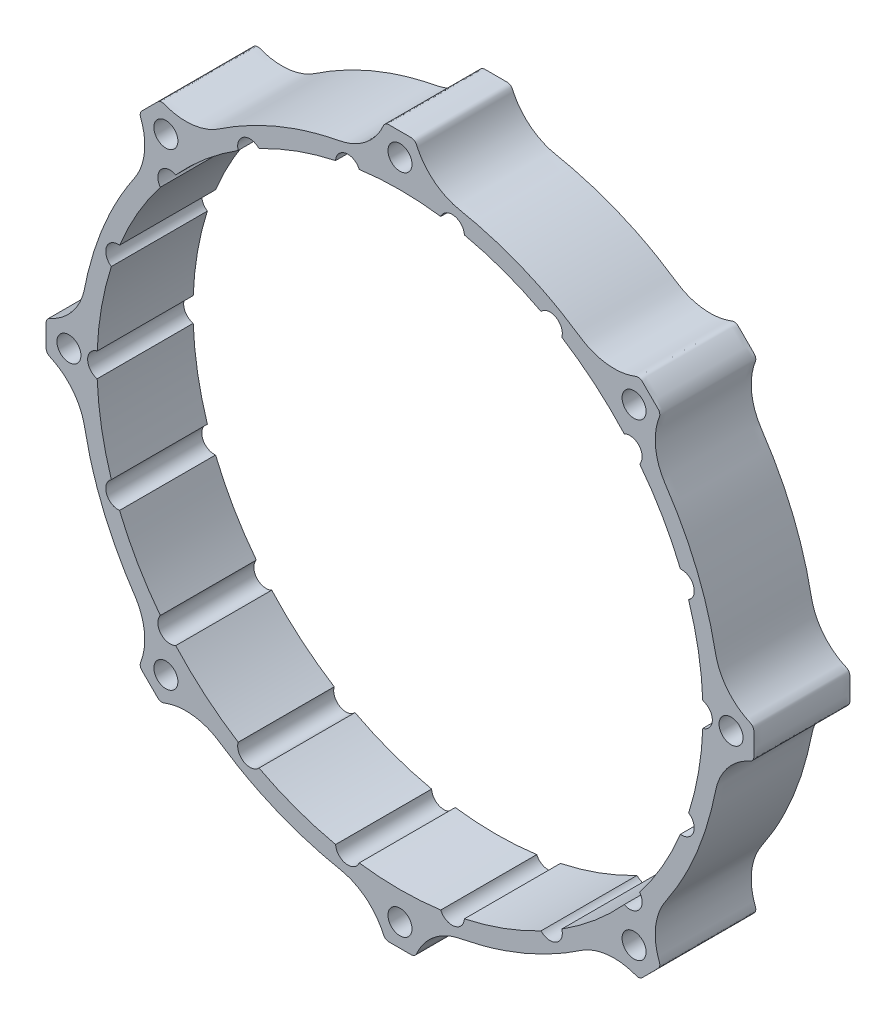
SolidWorks part; units mm, degrees
material "7075-T6, Plate (SS)"
ref_plane "Front Plane" through (0, 0, 0) normal (0, 0, 1) x (1, 0, 0)
ref_plane "Top Plane" through (0, 0, 0) normal (0, 1, 0) x (1, 0, 0)
ref_plane "Right Plane" through (0, 0, 0) normal (1, 0, 0) x (0, 0, -1)
sketch "Sketch1" plane through (0, 0, 0) normal (0, 0, 1) x (1, 0, 0)
  line L0 (0, 0) -> (0, 55.17) construction
  line L1 (0, 0) -> (-8.6824, 49.2404) construction
  arc A0 (-6.7951, 50.0407) -> (-10.7296, 49.347) centre (-8.6824, 49.2404) ccw
  arc A36 (-10.7296, 49.347) -> (-23.5003, 44.6989) centre (0, 0) ccw
  circle A53 centre (0, 0) radius 50 construction
  arc A54 (10.7296, 49.347) -> (6.7951, 50.0407) centre (8.6824, 49.2404) ccw
  arc A55 (26.9602, 42.7012) -> (23.5003, 44.6989) centre (25, 43.3013) ccw
  arc A56 (39.939, 30.9051) -> (37.3709, 33.9656) centre (38.3022, 32.1394) ccw
  arc A57 (48.1006, 15.3814) -> (46.7341, 19.1356) centre (46.9846, 17.101) ccw
  arc A58 (50.4605, -1.9976) -> (50.4605, 1.9976) centre (50, 0) ccw
  arc A59 (46.7341, -19.1356) -> (48.1006, -15.3814) centre (46.9846, -17.101) ccw
  arc A60 (37.3709, -33.9656) -> (39.939, -30.9051) centre (38.3022, -32.1394) ccw
  arc A61 (23.5003, -44.6989) -> (26.9602, -42.7012) centre (25, -43.3013) ccw
  arc A62 (6.7951, -50.0407) -> (10.7296, -49.347) centre (8.6824, -49.2404) ccw
  arc A63 (-10.7296, -49.347) -> (-6.7951, -50.0407) centre (-8.6824, -49.2404) ccw
  arc A64 (-26.9602, -42.7012) -> (-23.5003, -44.6989) centre (-25, -43.3013) ccw
  arc A65 (-39.939, -30.9051) -> (-37.3709, -33.9656) centre (-38.3022, -32.1394) ccw
  arc A66 (-48.1006, -15.3814) -> (-46.7341, -19.1356) centre (-46.9846, -17.101) ccw
  arc A67 (-50.4605, 1.9976) -> (-50.4605, -1.9976) centre (-50, 0) ccw
  arc A68 (-46.7341, 19.1356) -> (-48.1006, 15.3814) centre (-46.9846, 17.101) ccw
  arc A69 (-37.3709, 33.9656) -> (-39.939, 30.9051) centre (-38.3022, 32.1394) ccw
  arc A70 (-23.5003, 44.6989) -> (-26.9602, 42.7012) centre (-25, 43.3013) ccw
  arc A71 (6.7951, 50.0407) -> (-6.7951, 50.0407) centre (0, 0) ccw
  arc A72 (23.5003, 44.6989) -> (10.7296, 49.347) centre (0, 0) ccw
  arc A73 (46.7341, 19.1356) -> (39.939, 30.9051) centre (0, 0) ccw
  arc A74 (37.3709, 33.9656) -> (26.9602, 42.7012) centre (0, 0) ccw
  arc A75 (50.4605, 1.9976) -> (48.1006, 15.3814) centre (0, 0) ccw
  arc A76 (48.1006, -15.3814) -> (50.4605, -1.9976) centre (0, 0) ccw
  arc A77 (39.939, -30.9051) -> (46.7341, -19.1356) centre (0, 0) ccw
  arc A78 (26.9602, -42.7012) -> (37.3709, -33.9656) centre (0, 0) ccw
  arc A79 (10.7296, -49.347) -> (23.5003, -44.6989) centre (0, 0) ccw
  arc A80 (-6.7951, -50.0407) -> (6.7951, -50.0407) centre (0, 0) ccw
  arc A81 (-23.5003, -44.6989) -> (-10.7296, -49.347) centre (0, 0) ccw
  arc A82 (-37.3709, -33.9656) -> (-26.9602, -42.7012) centre (0, 0) ccw
  arc A83 (-46.7341, -19.1356) -> (-39.939, -30.9051) centre (0, 0) ccw
  arc A84 (-50.4605, -1.9976) -> (-48.1006, -15.3814) centre (0, 0) ccw
  arc A85 (-48.1006, 15.3814) -> (-50.4605, 1.9976) centre (0, 0) ccw
  arc A86 (-39.939, 30.9051) -> (-46.7341, 19.1356) centre (0, 0) ccw
  arc A87 (-26.9602, 42.7012) -> (-37.3709, 33.9656) centre (0, 0) ccw
  spline S1 degree 3 poles (2.8886, 58.0903) (2.8604, 58.1497) (2.8053, 58.2691) (2.7273, 58.4532) (2.6522, 58.562) (2.6097, 58.6121) (2.4833, 58.7614) (2.3195, 58.8684) (2.132, 58.9243) (2.1013, 58.9334) (2.039, 58.9487) (1.9428, 58.9658) (1.8787, 58.9658) (1.8466, 58.9658) (1.8146, 58.9658) (1.7505, 58.9658) (1.6544, 58.9658) (1.5903, 58.9658) (1.5583, 58.9658) (0.5194, 58.9658) (-0.5194, 58.9658) (-1.5583, 58.9658) (-1.5903, 58.9658) (-1.6544, 58.9658) (-1.7505, 58.9658) (-1.8146, 58.9658) (-1.8466, 58.9658) (-1.8787, 58.9658) (-1.9428, 58.9658) (-2.039, 58.9487) (-2.1013, 58.9334) (-2.132, 58.9243) (-2.3195, 58.8684) (-2.4833, 58.7614) (-2.6097, 58.6121) (-2.6522, 58.562) (-2.7273, 58.4532) (-2.8053, 58.2691) (-2.8604, 58.1497) (-2.8886, 58.0903) (-3.9043, 55.9453) (-5.5918, 54.2764) (-7.7481, 53.2847) (-8.2352, 53.0607) (-9.2456, 52.691) (-10.8423, 52.3981) (-11.8892, 52.165) (-12.4107, 52.0406) (-17.936, 50.7229) (-23.1839, 48.5492) (-28.0226, 45.574) (-28.4793, 45.2931) (-29.3844, 44.7177) (-30.7205, 43.7957) (-31.6964, 43.3428) (-32.1993, 43.1567) (-34.5203, 42.2981) (-36.9949, 42.3196) (-39.3007, 43.2183) (-39.3011, 43.2185) (-39.3019, 43.2188) (-39.3031, 43.2193) (-39.3039, 43.2196) (-39.3043, 43.2198) (-39.3047, 43.2199) (-39.3055, 43.2202) (-39.3067, 43.2207) (-39.3075, 43.221) (-39.3079, 43.2212) (-39.3103, 43.2221) (-39.3127, 43.223) (-39.3151, 43.224) (-39.3155, 43.2241) (-39.3163, 43.2245) (-39.3175, 43.2249) (-39.3183, 43.2252) (-39.3187, 43.2254) (-39.3191, 43.2255) (-39.3199, 43.2259) (-39.3211, 43.2263) (-39.3219, 43.2266) (-39.3224, 43.2268) (-39.5998, 43.3338) (-39.8966, 43.3148) (-40.1582, 43.1733) (-40.1864, 43.158) (-40.2413, 43.1248) (-40.3214, 43.0689) (-40.3667, 43.0236) (-40.3894, 43.0009) (-40.412, 42.9783) (-40.4573, 42.933) (-40.5253, 42.865) (-40.5706, 42.8197) (-40.5933, 42.797) (-41.3279, 42.0624) (-42.0624, 41.3279) (-42.797, 40.5933) (-42.8197, 40.5706) (-42.865, 40.5253) (-42.933, 40.4573) (-42.9783, 40.412) (-43.0009, 40.3894) (-43.0236, 40.3667) (-43.0689, 40.3214) (-43.1248, 40.2413) (-43.158, 40.1864) (-43.1733, 40.1582) (-43.3148, 39.8966) (-43.3338, 39.5998) (-43.2268, 39.3224) (-43.2266, 39.3219) (-43.2263, 39.3211) (-43.2259, 39.3199) (-43.2255, 39.3191) (-43.2254, 39.3187) (-43.2252, 39.3183) (-43.2249, 39.3175) (-43.2245, 39.3163) (-43.2241, 39.3155) (-43.224, 39.3151) (-43.223, 39.3127) (-43.2221, 39.3103) (-43.2212, 39.3079) (-43.221, 39.3075) (-43.2207, 39.3067) (-43.2202, 39.3055) (-43.2199, 39.3047) (-43.2198, 39.3043) (-43.2196, 39.3039) (-43.2193, 39.3031) (-43.2188, 39.3019) (-43.2185, 39.3011) (-43.2183, 39.3007) (-42.3196, 36.9949) (-42.2981, 34.5203) (-43.1567, 32.1993) (-43.3428, 31.6964) (-43.7957, 30.7205) (-44.7177, 29.3844) (-45.2931, 28.4793) (-45.574, 28.0226) (-48.5492, 23.1839) (-50.7229, 17.936) (-52.0406, 12.4107) (-52.165, 11.8892) (-52.3981, 10.8423) (-52.691, 9.2456) (-53.0607, 8.2352) (-53.2847, 7.7481) (-54.3188, 5.4997) (-56.0838, 3.7651) (-58.3498, 2.7702) (-58.3502, 2.77) (-58.3509, 2.7697) (-58.3521, 2.7692) (-58.3529, 2.7688) (-58.3533, 2.7687) (-58.3537, 2.7685) (-58.3545, 2.7681) (-58.3557, 2.7676) (-58.3565, 2.7673) (-58.3569, 2.7671) (-58.3592, 2.7661) (-58.3616, 2.765) (-58.364, 2.764) (-58.3644, 2.7638) (-58.3651, 2.7635) (-58.3663, 2.7629) (-58.3671, 2.7626) (-58.3675, 2.7624) (-58.3679, 2.7623) (-58.3687, 2.7619) (-58.3699, 2.7614) (-58.3707, 2.761) (-58.3711, 2.7609) (-58.643, 2.6403) (-58.8394, 2.417) (-58.9243, 2.132) (-58.9334, 2.1013) (-58.9487, 2.039) (-58.9658, 1.9428) (-58.9658, 1.8787) (-58.9658, 1.8466) (-58.9658, 1.8146) (-58.9658, 1.7505) (-58.9658, 1.6544) (-58.9658, 1.5903) (-58.9658, 1.5583) (-58.9658, 0.5194) (-58.9658, -0.5194) (-58.9658, -1.5583) (-58.9658, -1.5903) (-58.9658, -1.6544) (-58.9658, -1.7505) (-58.9658, -1.8146) (-58.9658, -1.8466) (-58.9658, -1.8787) (-58.9658, -1.9428) (-58.9487, -2.039) (-58.9334, -2.1013) (-58.9243, -2.132) (-58.8394, -2.417) (-58.643, -2.6403) (-58.3711, -2.7609) (-58.3707, -2.761) (-58.3699, -2.7614) (-58.3687, -2.7619) (-58.3679, -2.7623) (-58.3675, -2.7624) (-58.3671, -2.7626) (-58.3663, -2.7629) (-58.3651, -2.7635) (-58.3644, -2.7638) (-58.364, -2.764) (-58.3616, -2.765) (-58.3592, -2.7661) (-58.3569, -2.7671) (-58.3565, -2.7673) (-58.3557, -2.7676) (-58.3545, -2.7681) (-58.3537, -2.7685) (-58.3533, -2.7687) (-58.3529, -2.7688) (-58.3521, -2.7692) (-58.3509, -2.7697) (-58.3502, -2.77) (-58.3498, -2.7702) (-56.0838, -3.7651) (-54.3188, -5.4997) (-53.2847, -7.7481) (-53.0607, -8.2352) (-52.691, -9.2456) (-52.3981, -10.8423) (-52.165, -11.8892) (-52.0406, -12.4107) (-50.7229, -17.936) (-48.5492, -23.1839) (-45.574, -28.0226) (-45.2931, -28.4793) (-44.7177, -29.3844) (-43.7957, -30.7205) (-43.3428, -31.6964) (-43.1567, -32.1993) (-42.2981, -34.5203) (-42.3196, -36.9949) (-43.2183, -39.3007) (-43.2185, -39.3011) (-43.2188, -39.3019) (-43.2193, -39.3031) (-43.2196, -39.3039) (-43.2198, -39.3043) (-43.2199, -39.3047) (-43.2202, -39.3055) (-43.2207, -39.3067) (-43.221, -39.3075) (-43.2212, -39.3079) (-43.2221, -39.3103) (-43.223, -39.3127) (-43.224, -39.3151) (-43.2241, -39.3155) (-43.2245, -39.3163) (-43.2249, -39.3175) (-43.2252, -39.3183) (-43.2254, -39.3187) (-43.2255, -39.3191) (-43.2259, -39.3199) (-43.2263, -39.3211) (-43.2266, -39.3219) (-43.2268, -39.3224) (-43.3338, -39.5998) (-43.3148, -39.8966) (-43.1733, -40.1582) (-43.158, -40.1864) (-43.1248, -40.2413) (-43.0689, -40.3214) (-43.0236, -40.3667) (-43.0009, -40.3894) (-42.9783, -40.412) (-42.933, -40.4573) (-42.865, -40.5253) (-42.8197, -40.5706) (-42.797, -40.5933) (-42.0624, -41.3279) (-41.3279, -42.0624) (-40.5933, -42.797) (-40.5706, -42.8197) (-40.5253, -42.865) (-40.4573, -42.933) (-40.412, -42.9783) (-40.3894, -43.0009) (-40.3667, -43.0236) (-40.3214, -43.0689) (-40.2413, -43.1248) (-40.1864, -43.158) (-40.1582, -43.1733) (-39.8966, -43.3148) (-39.5998, -43.3338) (-39.3224, -43.2268) (-39.3219, -43.2266) (-39.3211, -43.2263) (-39.3199, -43.2259) (-39.3191, -43.2255) (-39.3187, -43.2254) (-39.3183, -43.2252) (-39.3175, -43.2249) (-39.3163, -43.2245) (-39.3155, -43.2241) (-39.3151, -43.224) (-39.3127, -43.223) (-39.3103, -43.2221) (-39.3079, -43.2212) (-39.3075, -43.221) (-39.3067, -43.2207) (-39.3055, -43.2202) (-39.3047, -43.2199) (-39.3043, -43.2198) (-39.3039, -43.2196) (-39.3031, -43.2193) (-39.3019, -43.2188) (-39.3011, -43.2185) (-39.3007, -43.2183) (-36.9949, -42.3196) (-34.5203, -42.2981) (-32.1993, -43.1567) (-31.6964, -43.3428) (-30.7205, -43.7957) (-29.3844, -44.7177) (-28.4793, -45.2931) (-28.0226, -45.574) (-23.1839, -48.5492) (-17.936, -50.7229) (-12.4107, -52.0406) (-11.8892, -52.165) (-10.8423, -52.3981) (-9.2456, -52.691) (-8.2352, -53.0607) (-7.7481, -53.2847) (-5.4997, -54.3188) (-3.7651, -56.0838) (-2.7702, -58.3498) (-2.77, -58.3502) (-2.7697, -58.3509) (-2.7692, -58.3521) (-2.7688, -58.3529) (-2.7687, -58.3533) (-2.7685, -58.3537) (-2.7681, -58.3545) (-2.7676, -58.3557) (-2.7673, -58.3565) (-2.7671, -58.3569) (-2.7661, -58.3592) (-2.765, -58.3616) (-2.764, -58.364) (-2.7638, -58.3644) (-2.7635, -58.3651) (-2.7629, -58.3663) (-2.7626, -58.3671) (-2.7624, -58.3675) (-2.7623, -58.3679) (-2.7619, -58.3687) (-2.7614, -58.3699) (-2.761, -58.3707) (-2.7609, -58.3711) (-2.6403, -58.643) (-2.417, -58.8394) (-2.132, -58.9243) (-2.1013, -58.9334) (-2.039, -58.9487) (-1.9428, -58.9658) (-1.8787, -58.9658) (-1.8466, -58.9658) (-1.8146, -58.9658) (-1.7505, -58.9658) (-1.6544, -58.9658) (-1.5903, -58.9658) (-1.5583, -58.9658) (-0.5194, -58.9658) (0.5194, -58.9658) (1.5583, -58.9658) (1.5903, -58.9658) (1.6544, -58.9658) (1.7505, -58.9658) (1.8146, -58.9658) (1.8466, -58.9658) (1.8787, -58.9658) (1.9428, -58.9658) (2.039, -58.9487) (2.1013, -58.9334) (2.132, -58.9243) (2.417, -58.8394) (2.6403, -58.643) (2.7609, -58.3711) (2.761, -58.3707) (2.7614, -58.3699) (2.7619, -58.3687) (2.7623, -58.3679) (2.7624, -58.3675) (2.7626, -58.3671) (2.7629, -58.3663) (2.7635, -58.3651) (2.7638, -58.3644) (2.764, -58.364) (2.765, -58.3616) (2.7661, -58.3592) (2.7671, -58.3569) (2.7673, -58.3565) (2.7676, -58.3557) (2.7681, -58.3545) (2.7685, -58.3537) (2.7687, -58.3533) (2.7688, -58.3529) (2.7692, -58.3521) (2.7697, -58.3509) (2.77, -58.3502) (2.7702, -58.3498) (3.7651, -56.0838) (5.4997, -54.3188) (7.7481, -53.2847) (8.2352, -53.0607) (9.2456, -52.691) (10.8423, -52.3981) (11.8892, -52.165) (12.4107, -52.0406) (17.936, -50.7229) (23.1839, -48.5492) (28.0226, -45.574) (28.4793, -45.2931) (29.3844, -44.7177) (30.7205, -43.7957) (31.6964, -43.3428) (32.1993, -43.1567) (34.5203, -42.2981) (36.9949, -42.3196) (39.3007, -43.2183) (39.3011, -43.2185) (39.3019, -43.2188) (39.3031, -43.2193) (39.3039, -43.2196) (39.3043, -43.2198) (39.3047, -43.2199) (39.3055, -43.2202) (39.3067, -43.2207) (39.3075, -43.221) (39.3079, -43.2212) (39.3103, -43.2221) (39.3127, -43.223) (39.3151, -43.224) (39.3155, -43.2241) (39.3163, -43.2245) (39.3175, -43.2249) (39.3183, -43.2252) (39.3187, -43.2254) (39.3191, -43.2255) (39.3199, -43.2259) (39.3211, -43.2263) (39.3219, -43.2266) (39.3224, -43.2268) (39.5998, -43.3338) (39.8966, -43.3148) (40.1582, -43.1733) (40.1864, -43.158) (40.2413, -43.1248) (40.3214, -43.0689) (40.3667, -43.0236) (40.3894, -43.0009) (40.412, -42.9783) (40.4573, -42.933) (40.5253, -42.865) (40.5706, -42.8197) (40.5933, -42.797) (41.3279, -42.0624) (42.0624, -41.3279) (42.797, -40.5933) (42.8197, -40.5706) (42.865, -40.5253) (42.933, -40.4573) (42.9783, -40.412) (43.0009, -40.3894) (43.0236, -40.3667) (43.0689, -40.3214) (43.1248, -40.2413) (43.158, -40.1864) (43.1733, -40.1582) (43.3148, -39.8966) (43.3338, -39.5998) (43.2268, -39.3224) (43.2266, -39.3219) (43.2263, -39.3211) (43.2259, -39.3199) (43.2255, -39.3191) (43.2254, -39.3187) (43.2252, -39.3183) (43.2249, -39.3175) (43.2245, -39.3163) (43.2241, -39.3155) (43.224, -39.3151) (43.223, -39.3127) (43.2221, -39.3103) (43.2212, -39.3079) (43.221, -39.3075) (43.2207, -39.3067) (43.2202, -39.3055) (43.2199, -39.3047) (43.2198, -39.3043) (43.2196, -39.3039) (43.2193, -39.3031) (43.2188, -39.3019) (43.2185, -39.3011) (43.2183, -39.3007) (42.3196, -36.9949) (42.2981, -34.5203) (43.1567, -32.1993) (43.3428, -31.6964) (43.7957, -30.7205) (44.7177, -29.3844) (45.2931, -28.4793) (45.574, -28.0226) (48.5492, -23.1839) (50.7229, -17.936) (52.0406, -12.4107) (52.165, -11.8892) (52.3981, -10.8423) (52.691, -9.2456) (53.0607, -8.2352) (53.2847, -7.7481) (54.3188, -5.4997) (56.0838, -3.7651) (58.3498, -2.7702) (58.3502, -2.77) (58.3509, -2.7697) (58.3521, -2.7692) (58.3529, -2.7688) (58.3533, -2.7687) (58.3537, -2.7685) (58.3545, -2.7681) (58.3557, -2.7676) (58.3565, -2.7673) (58.3569, -2.7671) (58.3592, -2.7661) (58.3616, -2.765) (58.364, -2.764) (58.3644, -2.7638) (58.3651, -2.7635) (58.3663, -2.7629) (58.3671, -2.7626) (58.3675, -2.7624) (58.3679, -2.7623) (58.3687, -2.7619) (58.3699, -2.7614) (58.3707, -2.761) (58.3711, -2.7609) (58.643, -2.6403) (58.8394, -2.417) (58.9243, -2.132) (58.9334, -2.1013) (58.9487, -2.039) (58.9658, -1.9428) (58.9658, -1.8787) (58.9658, -1.8466) (58.9658, -1.8146) (58.9658, -1.7505) (58.9658, -1.6544) (58.9658, -1.5903) (58.9658, -1.5583) (58.9658, -0.5194) (58.9658, 0.5194) (58.9658, 1.5583) (58.9658, 1.5903) (58.9658, 1.6544) (58.9658, 1.7505) (58.9658, 1.8146) (58.9658, 1.8466) (58.9658, 1.8787) (58.9658, 1.9428) (58.9487, 2.039) (58.9334, 2.1013) (58.9243, 2.132) (58.8394, 2.417) (58.643, 2.6403) (58.3711, 2.7609) (58.3707, 2.761) (58.3699, 2.7614) (58.3687, 2.7619) (58.3679, 2.7623) (58.3675, 2.7624) (58.3671, 2.7626) (58.3663, 2.7629) (58.3651, 2.7635) (58.3644, 2.7638) (58.364, 2.764) (58.3616, 2.765) (58.3592, 2.7661) (58.3569, 2.7671) (58.3565, 2.7673) (58.3557, 2.7676) (58.3545, 2.7681) (58.3537, 2.7685) (58.3533, 2.7687) (58.3529, 2.7688) (58.3521, 2.7692) (58.3509, 2.7697) (58.3502, 2.77) (58.3498, 2.7702) (56.0838, 3.7651) (54.3188, 5.4997) (53.2847, 7.7481) (53.0607, 8.2352) (52.691, 9.2456) (52.3981, 10.8423) (52.165, 11.8892) (52.0406, 12.4107) (50.7229, 17.936) (48.5492, 23.1839) (45.574, 28.0226) (45.2931, 28.4793) (44.7177, 29.3844) (43.7957, 30.7205) (43.3428, 31.6964) (43.1567, 32.1993) (42.2981, 34.5203) (42.3196, 36.9949) (43.2183, 39.3007) (43.2185, 39.3011) (43.2188, 39.3019) (43.2193, 39.3031) (43.2196, 39.3039) (43.2198, 39.3043) (43.2199, 39.3047) (43.2202, 39.3055) (43.2207, 39.3067) (43.221, 39.3075) (43.2212, 39.3079) (43.2221, 39.3103) (43.223, 39.3127) (43.224, 39.3151) (43.2241, 39.3155) (43.2245, 39.3163) (43.2249, 39.3175) (43.2252, 39.3183) (43.2254, 39.3187) (43.2255, 39.3191) (43.2259, 39.3199) (43.2263, 39.3211) (43.2266, 39.3219) (43.2268, 39.3224) (43.3338, 39.5998) (43.3148, 39.8966) (43.1733, 40.1582) (43.158, 40.1864) (43.1248, 40.2413) (43.0689, 40.3214) (43.0236, 40.3667) (43.0009, 40.3894) (42.9783, 40.412) (42.933, 40.4573) (42.865, 40.5253) (42.8197, 40.5706) (42.797, 40.5933) (42.0624, 41.3279) (41.3279, 42.0624) (40.5933, 42.797) (40.5706, 42.8197) (40.5253, 42.865) (40.4573, 42.933) (40.412, 42.9783) (40.3894, 43.0009) (40.3667, 43.0236) (40.3214, 43.0689) (40.2413, 43.1248) (40.1864, 43.158) (40.1582, 43.1733) (39.8966, 43.3148) (39.5998, 43.3338) (39.3224, 43.2268) (39.3219, 43.2266) (39.3211, 43.2263) (39.3199, 43.2259) (39.3191, 43.2255) (39.3187, 43.2254) (39.3183, 43.2252) (39.3175, 43.2249) (39.3163, 43.2245) (39.3155, 43.2241) (39.3151, 43.224) (39.3127, 43.223) (39.3103, 43.2221) (39.3079, 43.2212) (39.3075, 43.221) (39.3067, 43.2207) (39.3055, 43.2202) (39.3047, 43.2199) (39.3043, 43.2198) (39.3039, 43.2196) (39.3031, 43.2193) (39.3019, 43.2188) (39.3011, 43.2185) (39.3007, 43.2183) (36.9949, 42.3196) (34.5203, 42.2981) (32.1993, 43.1567) (31.6964, 43.3428) (30.7205, 43.7957) (29.3844, 44.7177) (28.4793, 45.2931) (28.0226, 45.574) (23.1839, 48.5492) (17.936, 50.7229) (12.4107, 52.0406) (11.8892, 52.165) (10.8423, 52.3981) (9.2456, 52.691) (8.2352, 53.0607) (7.7481, 53.2847) (5.5918, 54.2764) (3.9043, 55.9453) (2.8886, 58.0903) (2.8604, 58.1497) (2.8053, 58.2691) knots -0.018272 0 0 0 0.000527 0.001055 0.001582 0.001582 0.001582 0.003108 0.003108 0.003108 0.003365 0.003622 0.003879 0.003879 0.003879 0.004136 0.004393 0.00465 0.00465 0.00465 0.012982 0.012982 0.012982 0.013239 0.013496 0.013753 0.013753 0.013753 0.01401 0.014267 0.014524 0.014524 0.014524 0.01605 0.01605 0.01605 0.016577 0.017104 0.017632 0.017632 0.017632 0.035904 0.035904 0.035904 0.040205 0.044505 0.048806 0.048806 0.048806 0.093985 0.093985 0.093985 0.098286 0.102587 0.106888 0.106888 0.106888 0.125875 0.125875 0.125875 0.125878 0.125882 0.125885 0.125885 0.125885 0.125888 0.125892 0.125895 0.125895 0.125895 0.125916 0.125916 0.125916 0.12592 0.125923 0.125926 0.125926 0.125926 0.12593 0.125933 0.125937 0.125937 0.125937 0.128176 0.128176 0.128176 0.128433 0.12869 0.128947 0.128947 0.128947 0.129204 0.129461 0.129718 0.129718 0.129718 0.138051 0.138051 0.138051 0.138308 0.138565 0.138822 0.138822 0.138822 0.139079 0.139335 0.139592 0.139592 0.139592 0.141832 0.141832 0.141832 0.141835 0.141839 0.141842 0.141842 0.141842 0.141846 0.141849 0.141853 0.141853 0.141853 0.141873 0.141873 0.141873 0.141877 0.14188 0.141884 0.141884 0.141884 0.141887 0.141891 0.141894 0.141894 0.141894 0.160881 0.160881 0.160881 0.165182 0.169483 0.173783 0.173783 0.173783 0.218962 0.218962 0.218962 0.223263 0.227564 0.231865 0.231865 0.231865 0.250852 0.250852 0.250852 0.250855 0.250859 0.250862 0.250862 0.250862 0.250866 0.250869 0.250873 0.250873 0.250873 0.250893 0.250893 0.250893 0.250897 0.2509 0.250904 0.250904 0.250904 0.250907 0.250911 0.250914 0.250914 0.250914 0.253153 0.253153 0.253153 0.25341 0.253667 0.253924 0.253924 0.253924 0.254181 0.254438 0.254695 0.254695 0.254695 0.263028 0.263028 0.263028 0.263285 0.263542 0.263799 0.263799 0.263799 0.264056 0.264313 0.26457 0.26457 0.26457 0.266809 0.266809 0.266809 0.266812 0.266816 0.266819 0.266819 0.266819 0.266823 0.266826 0.26683 0.26683 0.26683 0.26685 0.26685 0.26685 0.266854 0.266857 0.266861 0.266861 0.266861 0.266864 0.266868 0.266871 0.266871 0.266871 0.285858 0.285858 0.285858 0.290159 0.29446 0.298761 0.298761 0.298761 0.34394 0.34394 0.34394 0.34824 0.352541 0.356842 0.356842 0.356842 0.375829 0.375829 0.375829 0.375832 0.375836 0.375839 0.375839 0.375839 0.375843 0.375846 0.37585 0.37585 0.37585 0.37587 0.37587 0.37587 0.375874 0.375877 0.375881 0.375881 0.375881 0.375884 0.375888 0.375891 0.375891 0.375891 0.37813 0.37813 0.37813 0.378387 0.378644 0.378901 0.378901 0.378901 0.379158 0.379415 0.379672 0.379672 0.379672 0.388005 0.388005 0.388005 0.388262 0.388519 0.388776 0.388776 0.388776 0.389033 0.38929 0.389547 0.389547 0.389547 0.391786 0.391786 0.391786 0.39179 0.391793 0.391797 0.391797 0.391797 0.3918 0.391803 0.391807 0.391807 0.391807 0.391828 0.391828 0.391828 0.391831 0.391834 0.391838 0.391838 0.391838 0.391841 0.391845 0.391848 0.391848 0.391848 0.410835 0.410835 0.410835 0.415136 0.419437 0.423738 0.423738 0.423738 0.468917 0.468917 0.468917 0.473217 0.477518 0.481819 0.481819 0.481819 0.500806 0.500806 0.500806 0.50081 0.500813 0.500816 0.500816 0.500816 0.50082 0.500823 0.500827 0.500827 0.500827 0.500848 0.500848 0.500848 0.500851 0.500854 0.500858 0.500858 0.500858 0.500861 0.500865 0.500868 0.500868 0.500868 0.503108 0.503108 0.503108 0.503365 0.503622 0.503879 0.503879 0.503879 0.504136 0.504393 0.50465 0.50465 0.50465 0.512982 0.512982 0.512982 0.513239 0.513496 0.513753 0.513753 0.513753 0.51401 0.514267 0.514524 0.514524 0.514524 0.516763 0.516763 0.516763 0.516767 0.51677 0.516774 0.516774 0.516774 0.516777 0.516781 0.516784 0.516784 0.516784 0.516805 0.516805 0.516805 0.516808 0.516812 0.516815 0.516815 0.516815 0.516819 0.516822 0.516825 0.516825 0.516825 0.535813 0.535813 0.535813 0.540113 0.544414 0.548715 0.548715 0.548715 0.593894 0.593894 0.593894 0.598195 0.602495 0.606796 0.606796 0.606796 0.625783 0.625783 0.625783 0.625787 0.62579 0.625794 0.625794 0.625794 0.625797 0.625801 0.625804 0.625804 0.625804 0.625825 0.625825 0.625825 0.625828 0.625832 0.625835 0.625835 0.625835 0.625839 0.625842 0.625845 0.625845 0.625845 0.628085 0.628085 0.628085 0.628342 0.628599 0.628856 0.628856 0.628856 0.629113 0.62937 0.629627 0.629627 0.629627 0.637959 0.637959 0.637959 0.638216 0.638473 0.63873 0.63873 0.63873 0.638987 0.639244 0.639501 0.639501 0.639501 0.64174 0.64174 0.64174 0.641744 0.641747 0.641751 0.641751 0.641751 0.641754 0.641758 0.641761 0.641761 0.641761 0.641782 0.641782 0.641782 0.641785 0.641789 0.641792 0.641792 0.641792 0.641796 0.641799 0.641803 0.641803 0.641803 0.66079 0.66079 0.66079 0.66509 0.669391 0.673692 0.673692 0.673692 0.718871 0.718871 0.718871 0.723172 0.727473 0.731773 0.731773 0.731773 0.75076 0.75076 0.75076 0.750764 0.750767 0.750771 0.750771 0.750771 0.750774 0.750778 0.750781 0.750781 0.750781 0.750802 0.750802 0.750802 0.750805 0.750809 0.750812 0.750812 0.750812 0.750816 0.750819 0.750823 0.750823 0.750823 0.753062 0.753062 0.753062 0.753319 0.753576 0.753833 0.753833 0.753833 0.75409 0.754347 0.754604 0.754604 0.754604 0.762936 0.762936 0.762936 0.763193 0.76345 0.763707 0.763707 0.763707 0.763964 0.764221 0.764478 0.764478 0.764478 0.766718 0.766718 0.766718 0.766721 0.766725 0.766728 0.766728 0.766728 0.766731 0.766735 0.766738 0.766738 0.766738 0.766759 0.766759 0.766759 0.766763 0.766766 0.766769 0.766769 0.766769 0.766773 0.766776 0.76678 0.76678 0.76678 0.785767 0.785767 0.785767 0.790068 0.794368 0.798669 0.798669 0.798669 0.843848 0.843848 0.843848 0.848149 0.85245 0.85675 0.85675 0.85675 0.875738 0.875738 0.875738 0.875741 0.875744 0.875748 0.875748 0.875748 0.875751 0.875755 0.875758 0.875758 0.875758 0.875779 0.875779 0.875779 0.875782 0.875786 0.875789 0.875789 0.875789 0.875793 0.875796 0.8758 0.8758 0.8758 0.878039 0.878039 0.878039 0.878296 0.878553 0.87881 0.87881 0.87881 0.879067 0.879324 0.879581 0.879581 0.879581 0.887913 0.887913 0.887913 0.88817 0.888427 0.888684 0.888684 0.888684 0.888941 0.889198 0.889455 0.889455 0.889455 0.891695 0.891695 0.891695 0.891698 0.891702 0.891705 0.891705 0.891705 0.891709 0.891712 0.891715 0.891715 0.891715 0.891736 0.891736 0.891736 0.89174 0.891743 0.891747 0.891747 0.891747 0.89175 0.891753 0.891757 0.891757 0.891757 0.910744 0.910744 0.910744 0.915045 0.919346 0.923646 0.923646 0.923646 0.968825 0.968825 0.968825 0.973126 0.977427 0.981728 0.981728 0.981728 1 1 1 1.000527 1.001055 1.001582 weights 1 1 1 1 1 1 0.972283 0.972283 1 1 1 1 1 1 1 1 1 1 1 1 1 1 1 1 1 1 1 1 1 1 1 1 0.972283 0.972283 1 1 1 1 1 1 0.959869 0.959869 1 1 1 1 1 1 0.991634 0.991634 1 1 1 1 1 1 0.956557 0.956557 1 1 1 1 1 1 1 1 1 1 1 1 1 1 1 1 1 1 1 1 1 1 1 1 0.938724 0.938724 1 1 1 1 1 1 1 1 1 1 1 1 1 1 1 1 1 1 1 1 1 1 1 1 0.938724 0.938724 1 1 1 1 1 1 1 1 1 1 1 1 1 1 1 1 1 1 1 1 1 1 1 1 0.956557 0.956557 1 1 1 1 1 1 0.991634 0.991634 1 1 1 1 1 1 0.956557 0.956557 1 1 1 1 1 1 1 1 1 1 1 1 1 1 1 1 1 1 1 1 1 1 1 1 0.938724 0.938724 1 1 1 1 1 1 1 1 1 1 1 1 1 1 1 1 1 1 1 1 1 1 1 1 0.938724 0.938724 1 1 1 1 1 1 1 1 1 1 1 1 1 1 1 1 1 1 1 1 1 1 1 1 0.956557 0.956557 1 1 1 1 1 1 0.991634 0.991634 1 1 1 1 1 1 0.956557 0.956557 1 1 1 1 1 1 1 1 1 1 1 1 1 1 1 1 1 1 1 1 1 1 1 1 0.938724 0.938724 1 1 1 1 1 1 1 1 1 1 1 1 1 1 1 1 1 1 1 1 1 1 1 1 0.938724 0.938724 1 1 1 1 1 1 1 1 1 1 1 1 1 1 1 1 1 1 1 1 1 1 1 1 0.956557 0.956557 1 1 1 1 1 1 0.991634 0.991634 1 1 1 1 1 1 0.956557 0.956557 1 1 1 1 1 1 1 1 1 1 1 1 1 1 1 1 1 1 1 1 1 1 1 1 0.938724 0.938724 1 1 1 1 1 1 1 1 1 1 1 1 1 1 1 1 1 1 1 1 1 1 1 1 0.938724 0.938724 1 1 1 1 1 1 1 1 1 1 1 1 1 1 1 1 1 1 1 1 1 1 1 1 0.956557 0.956557 1 1 1 1 1 1 0.991634 0.991634 1 1 1 1 1 1 0.956557 0.956557 1 1 1 1 1 1 1 1 1 1 1 1 1 1 1 1 1 1 1 1 1 1 1 1 0.938724 0.938724 1 1 1 1 1 1 1 1 1 1 1 1 1 1 1 1 1 1 1 1 1 1 1 1 0.938724 0.938724 1 1 1 1 1 1 1 1 1 1 1 1 1 1 1 1 1 1 1 1 1 1 1 1 0.956557 0.956557 1 1 1 1 1 1 0.991634 0.991634 1 1 1 1 1 1 0.956557 0.956557 1 1 1 1 1 1 1 1 1 1 1 1 1 1 1 1 1 1 1 1 1 1 1 1 0.938724 0.938724 1 1 1 1 1 1 1 1 1 1 1 1 1 1 1 1 1 1 1 1 1 1 1 1 0.938724 0.938724 1 1 1 1 1 1 1 1 1 1 1 1 1 1 1 1 1 1 1 1 1 1 1 1 0.956557 0.956557 1 1 1 1 1 1 0.991634 0.991634 1 1 1 1 1 1 0.956557 0.956557 1 1 1 1 1 1 1 1 1 1 1 1 1 1 1 1 1 1 1 1 1 1 1 1 0.938724 0.938724 1 1 1 1 1 1 1 1 1 1 1 1 1 1 1 1 1 1 1 1 1 1 1 1 0.938724 0.938724 1 1 1 1 1 1 1 1 1 1 1 1 1 1 1 1 1 1 1 1 1 1 1 1 0.956557 0.956557 1 1 1 1 1 1 0.991634 0.991634 1 1 1 1 1 1 0.959869 0.959869 1 1 1 only from (2.8886, 58.0903) to (2.8886, 58.0903)
  spline S2 degree 3 poles (2.8886, 58.0903) (2.8604, 58.1497) (2.8053, 58.2691) (2.7273, 58.4532) (2.6522, 58.562) (2.6097, 58.6121) (2.4833, 58.7614) (2.3195, 58.8684) (2.132, 58.9243) (2.1013, 58.9334) (2.039, 58.9487) (1.9428, 58.9658) (1.8787, 58.9658) (1.8466, 58.9658) (1.8146, 58.9658) (1.7505, 58.9658) (1.6544, 58.9658) (1.5903, 58.9658) (1.5583, 58.9658) (0.5194, 58.9658) (-0.5194, 58.9658) (-1.5583, 58.9658) (-1.5903, 58.9658) (-1.6544, 58.9658) (-1.7505, 58.9658) (-1.8146, 58.9658) (-1.8466, 58.9658) (-1.8787, 58.9658) (-1.9428, 58.9658) (-2.039, 58.9487) (-2.1013, 58.9334) (-2.132, 58.9243) (-2.3195, 58.8684) (-2.4833, 58.7614) (-2.6097, 58.6121) (-2.6522, 58.562) (-2.7273, 58.4532) (-2.8053, 58.2691) (-2.8604, 58.1497) (-2.8886, 58.0903) (-3.9043, 55.9453) (-5.5918, 54.2764) (-7.7481, 53.2847) (-8.2352, 53.0607) (-9.2456, 52.691) (-10.8423, 52.3981) (-11.8892, 52.165) (-12.4107, 52.0406) (-17.936, 50.7229) (-23.1839, 48.5492) (-28.0226, 45.574) (-28.4793, 45.2931) (-29.3844, 44.7177) (-30.7205, 43.7957) (-31.6964, 43.3428) (-32.1993, 43.1567) (-34.5203, 42.2981) (-36.9949, 42.3196) (-39.3007, 43.2183) (-39.3011, 43.2185) (-39.3019, 43.2188) (-39.3031, 43.2193) (-39.3039, 43.2196) (-39.3043, 43.2198) (-39.3047, 43.2199) (-39.3055, 43.2202) (-39.3067, 43.2207) (-39.3075, 43.221) (-39.3079, 43.2212) (-39.3103, 43.2221) (-39.3127, 43.223) (-39.3151, 43.224) (-39.3155, 43.2241) (-39.3163, 43.2245) (-39.3175, 43.2249) (-39.3183, 43.2252) (-39.3187, 43.2254) (-39.3191, 43.2255) (-39.3199, 43.2259) (-39.3211, 43.2263) (-39.3219, 43.2266) (-39.3224, 43.2268) (-39.5998, 43.3338) (-39.8966, 43.3148) (-40.1582, 43.1733) (-40.1864, 43.158) (-40.2413, 43.1248) (-40.3214, 43.0689) (-40.3667, 43.0236) (-40.3894, 43.0009) (-40.412, 42.9783) (-40.4573, 42.933) (-40.5253, 42.865) (-40.5706, 42.8197) (-40.5933, 42.797) (-41.3279, 42.0624) (-42.0624, 41.3279) (-42.797, 40.5933) (-42.8197, 40.5706) (-42.865, 40.5253) (-42.933, 40.4573) (-42.9783, 40.412) (-43.0009, 40.3894) (-43.0236, 40.3667) (-43.0689, 40.3214) (-43.1248, 40.2413) (-43.158, 40.1864) (-43.1733, 40.1582) (-43.3148, 39.8966) (-43.3338, 39.5998) (-43.2268, 39.3224) (-43.2266, 39.3219) (-43.2263, 39.3211) (-43.2259, 39.3199) (-43.2255, 39.3191) (-43.2254, 39.3187) (-43.2252, 39.3183) (-43.2249, 39.3175) (-43.2245, 39.3163) (-43.2241, 39.3155) (-43.224, 39.3151) (-43.223, 39.3127) (-43.2221, 39.3103) (-43.2212, 39.3079) (-43.221, 39.3075) (-43.2207, 39.3067) (-43.2202, 39.3055) (-43.2199, 39.3047) (-43.2198, 39.3043) (-43.2196, 39.3039) (-43.2193, 39.3031) (-43.2188, 39.3019) (-43.2185, 39.3011) (-43.2183, 39.3007) (-42.3196, 36.9949) (-42.2981, 34.5203) (-43.1567, 32.1993) (-43.3428, 31.6964) (-43.7957, 30.7205) (-44.7177, 29.3844) (-45.2931, 28.4793) (-45.574, 28.0226) (-48.5492, 23.1839) (-50.7229, 17.936) (-52.0406, 12.4107) (-52.165, 11.8892) (-52.3981, 10.8423) (-52.691, 9.2456) (-53.0607, 8.2352) (-53.2847, 7.7481) (-54.3188, 5.4997) (-56.0838, 3.7651) (-58.3498, 2.7702) (-58.3502, 2.77) (-58.3509, 2.7697) (-58.3521, 2.7692) (-58.3529, 2.7688) (-58.3533, 2.7687) (-58.3537, 2.7685) (-58.3545, 2.7681) (-58.3557, 2.7676) (-58.3565, 2.7673) (-58.3569, 2.7671) (-58.3592, 2.7661) (-58.3616, 2.765) (-58.364, 2.764) (-58.3644, 2.7638) (-58.3651, 2.7635) (-58.3663, 2.7629) (-58.3671, 2.7626) (-58.3675, 2.7624) (-58.3679, 2.7623) (-58.3687, 2.7619) (-58.3699, 2.7614) (-58.3707, 2.761) (-58.3711, 2.7609) (-58.643, 2.6403) (-58.8394, 2.417) (-58.9243, 2.132) (-58.9334, 2.1013) (-58.9487, 2.039) (-58.9658, 1.9428) (-58.9658, 1.8787) (-58.9658, 1.8466) (-58.9658, 1.8146) (-58.9658, 1.7505) (-58.9658, 1.6544) (-58.9658, 1.5903) (-58.9658, 1.5583) (-58.9658, 0.5194) (-58.9658, -0.5194) (-58.9658, -1.5583) (-58.9658, -1.5903) (-58.9658, -1.6544) (-58.9658, -1.7505) (-58.9658, -1.8146) (-58.9658, -1.8466) (-58.9658, -1.8787) (-58.9658, -1.9428) (-58.9487, -2.039) (-58.9334, -2.1013) (-58.9243, -2.132) (-58.8394, -2.417) (-58.643, -2.6403) (-58.3711, -2.7609) (-58.3707, -2.761) (-58.3699, -2.7614) (-58.3687, -2.7619) (-58.3679, -2.7623) (-58.3675, -2.7624) (-58.3671, -2.7626) (-58.3663, -2.7629) (-58.3651, -2.7635) (-58.3644, -2.7638) (-58.364, -2.764) (-58.3616, -2.765) (-58.3592, -2.7661) (-58.3569, -2.7671) (-58.3565, -2.7673) (-58.3557, -2.7676) (-58.3545, -2.7681) (-58.3537, -2.7685) (-58.3533, -2.7687) (-58.3529, -2.7688) (-58.3521, -2.7692) (-58.3509, -2.7697) (-58.3502, -2.77) (-58.3498, -2.7702) (-56.0838, -3.7651) (-54.3188, -5.4997) (-53.2847, -7.7481) (-53.0607, -8.2352) (-52.691, -9.2456) (-52.3981, -10.8423) (-52.165, -11.8892) (-52.0406, -12.4107) (-50.7229, -17.936) (-48.5492, -23.1839) (-45.574, -28.0226) (-45.2931, -28.4793) (-44.7177, -29.3844) (-43.7957, -30.7205) (-43.3428, -31.6964) (-43.1567, -32.1993) (-42.2981, -34.5203) (-42.3196, -36.9949) (-43.2183, -39.3007) (-43.2185, -39.3011) (-43.2188, -39.3019) (-43.2193, -39.3031) (-43.2196, -39.3039) (-43.2198, -39.3043) (-43.2199, -39.3047) (-43.2202, -39.3055) (-43.2207, -39.3067) (-43.221, -39.3075) (-43.2212, -39.3079) (-43.2221, -39.3103) (-43.223, -39.3127) (-43.224, -39.3151) (-43.2241, -39.3155) (-43.2245, -39.3163) (-43.2249, -39.3175) (-43.2252, -39.3183) (-43.2254, -39.3187) (-43.2255, -39.3191) (-43.2259, -39.3199) (-43.2263, -39.3211) (-43.2266, -39.3219) (-43.2268, -39.3224) (-43.3338, -39.5998) (-43.3148, -39.8966) (-43.1733, -40.1582) (-43.158, -40.1864) (-43.1248, -40.2413) (-43.0689, -40.3214) (-43.0236, -40.3667) (-43.0009, -40.3894) (-42.9783, -40.412) (-42.933, -40.4573) (-42.865, -40.5253) (-42.8197, -40.5706) (-42.797, -40.5933) (-42.0624, -41.3279) (-41.3279, -42.0624) (-40.5933, -42.797) (-40.5706, -42.8197) (-40.5253, -42.865) (-40.4573, -42.933) (-40.412, -42.9783) (-40.3894, -43.0009) (-40.3667, -43.0236) (-40.3214, -43.0689) (-40.2413, -43.1248) (-40.1864, -43.158) (-40.1582, -43.1733) (-39.8966, -43.3148) (-39.5998, -43.3338) (-39.3224, -43.2268) (-39.3219, -43.2266) (-39.3211, -43.2263) (-39.3199, -43.2259) (-39.3191, -43.2255) (-39.3187, -43.2254) (-39.3183, -43.2252) (-39.3175, -43.2249) (-39.3163, -43.2245) (-39.3155, -43.2241) (-39.3151, -43.224) (-39.3127, -43.223) (-39.3103, -43.2221) (-39.3079, -43.2212) (-39.3075, -43.221) (-39.3067, -43.2207) (-39.3055, -43.2202) (-39.3047, -43.2199) (-39.3043, -43.2198) (-39.3039, -43.2196) (-39.3031, -43.2193) (-39.3019, -43.2188) (-39.3011, -43.2185) (-39.3007, -43.2183) (-36.9949, -42.3196) (-34.5203, -42.2981) (-32.1993, -43.1567) (-31.6964, -43.3428) (-30.7205, -43.7957) (-29.3844, -44.7177) (-28.4793, -45.2931) (-28.0226, -45.574) (-23.1839, -48.5492) (-17.936, -50.7229) (-12.4107, -52.0406) (-11.8892, -52.165) (-10.8423, -52.3981) (-9.2456, -52.691) (-8.2352, -53.0607) (-7.7481, -53.2847) (-5.4997, -54.3188) (-3.7651, -56.0838) (-2.7702, -58.3498) (-2.77, -58.3502) (-2.7697, -58.3509) (-2.7692, -58.3521) (-2.7688, -58.3529) (-2.7687, -58.3533) (-2.7685, -58.3537) (-2.7681, -58.3545) (-2.7676, -58.3557) (-2.7673, -58.3565) (-2.7671, -58.3569) (-2.7661, -58.3592) (-2.765, -58.3616) (-2.764, -58.364) (-2.7638, -58.3644) (-2.7635, -58.3651) (-2.7629, -58.3663) (-2.7626, -58.3671) (-2.7624, -58.3675) (-2.7623, -58.3679) (-2.7619, -58.3687) (-2.7614, -58.3699) (-2.761, -58.3707) (-2.7609, -58.3711) (-2.6403, -58.643) (-2.417, -58.8394) (-2.132, -58.9243) (-2.1013, -58.9334) (-2.039, -58.9487) (-1.9428, -58.9658) (-1.8787, -58.9658) (-1.8466, -58.9658) (-1.8146, -58.9658) (-1.7505, -58.9658) (-1.6544, -58.9658) (-1.5903, -58.9658) (-1.5583, -58.9658) (-0.5194, -58.9658) (0.5194, -58.9658) (1.5583, -58.9658) (1.5903, -58.9658) (1.6544, -58.9658) (1.7505, -58.9658) (1.8146, -58.9658) (1.8466, -58.9658) (1.8787, -58.9658) (1.9428, -58.9658) (2.039, -58.9487) (2.1013, -58.9334) (2.132, -58.9243) (2.417, -58.8394) (2.6403, -58.643) (2.7609, -58.3711) (2.761, -58.3707) (2.7614, -58.3699) (2.7619, -58.3687) (2.7623, -58.3679) (2.7624, -58.3675) (2.7626, -58.3671) (2.7629, -58.3663) (2.7635, -58.3651) (2.7638, -58.3644) (2.764, -58.364) (2.765, -58.3616) (2.7661, -58.3592) (2.7671, -58.3569) (2.7673, -58.3565) (2.7676, -58.3557) (2.7681, -58.3545) (2.7685, -58.3537) (2.7687, -58.3533) (2.7688, -58.3529) (2.7692, -58.3521) (2.7697, -58.3509) (2.77, -58.3502) (2.7702, -58.3498) (3.7651, -56.0838) (5.4997, -54.3188) (7.7481, -53.2847) (8.2352, -53.0607) (9.2456, -52.691) (10.8423, -52.3981) (11.8892, -52.165) (12.4107, -52.0406) (17.936, -50.7229) (23.1839, -48.5492) (28.0226, -45.574) (28.4793, -45.2931) (29.3844, -44.7177) (30.7205, -43.7957) (31.6964, -43.3428) (32.1993, -43.1567) (34.5203, -42.2981) (36.9949, -42.3196) (39.3007, -43.2183) (39.3011, -43.2185) (39.3019, -43.2188) (39.3031, -43.2193) (39.3039, -43.2196) (39.3043, -43.2198) (39.3047, -43.2199) (39.3055, -43.2202) (39.3067, -43.2207) (39.3075, -43.221) (39.3079, -43.2212) (39.3103, -43.2221) (39.3127, -43.223) (39.3151, -43.224) (39.3155, -43.2241) (39.3163, -43.2245) (39.3175, -43.2249) (39.3183, -43.2252) (39.3187, -43.2254) (39.3191, -43.2255) (39.3199, -43.2259) (39.3211, -43.2263) (39.3219, -43.2266) (39.3224, -43.2268) (39.5998, -43.3338) (39.8966, -43.3148) (40.1582, -43.1733) (40.1864, -43.158) (40.2413, -43.1248) (40.3214, -43.0689) (40.3667, -43.0236) (40.3894, -43.0009) (40.412, -42.9783) (40.4573, -42.933) (40.5253, -42.865) (40.5706, -42.8197) (40.5933, -42.797) (41.3279, -42.0624) (42.0624, -41.3279) (42.797, -40.5933) (42.8197, -40.5706) (42.865, -40.5253) (42.933, -40.4573) (42.9783, -40.412) (43.0009, -40.3894) (43.0236, -40.3667) (43.0689, -40.3214) (43.1248, -40.2413) (43.158, -40.1864) (43.1733, -40.1582) (43.3148, -39.8966) (43.3338, -39.5998) (43.2268, -39.3224) (43.2266, -39.3219) (43.2263, -39.3211) (43.2259, -39.3199) (43.2255, -39.3191) (43.2254, -39.3187) (43.2252, -39.3183) (43.2249, -39.3175) (43.2245, -39.3163) (43.2241, -39.3155) (43.224, -39.3151) (43.223, -39.3127) (43.2221, -39.3103) (43.2212, -39.3079) (43.221, -39.3075) (43.2207, -39.3067) (43.2202, -39.3055) (43.2199, -39.3047) (43.2198, -39.3043) (43.2196, -39.3039) (43.2193, -39.3031) (43.2188, -39.3019) (43.2185, -39.3011) (43.2183, -39.3007) (42.3196, -36.9949) (42.2981, -34.5203) (43.1567, -32.1993) (43.3428, -31.6964) (43.7957, -30.7205) (44.7177, -29.3844) (45.2931, -28.4793) (45.574, -28.0226) (48.5492, -23.1839) (50.7229, -17.936) (52.0406, -12.4107) (52.165, -11.8892) (52.3981, -10.8423) (52.691, -9.2456) (53.0607, -8.2352) (53.2847, -7.7481) (54.3188, -5.4997) (56.0838, -3.7651) (58.3498, -2.7702) (58.3502, -2.77) (58.3509, -2.7697) (58.3521, -2.7692) (58.3529, -2.7688) (58.3533, -2.7687) (58.3537, -2.7685) (58.3545, -2.7681) (58.3557, -2.7676) (58.3565, -2.7673) (58.3569, -2.7671) (58.3592, -2.7661) (58.3616, -2.765) (58.364, -2.764) (58.3644, -2.7638) (58.3651, -2.7635) (58.3663, -2.7629) (58.3671, -2.7626) (58.3675, -2.7624) (58.3679, -2.7623) (58.3687, -2.7619) (58.3699, -2.7614) (58.3707, -2.761) (58.3711, -2.7609) (58.643, -2.6403) (58.8394, -2.417) (58.9243, -2.132) (58.9334, -2.1013) (58.9487, -2.039) (58.9658, -1.9428) (58.9658, -1.8787) (58.9658, -1.8466) (58.9658, -1.8146) (58.9658, -1.7505) (58.9658, -1.6544) (58.9658, -1.5903) (58.9658, -1.5583) (58.9658, -0.5194) (58.9658, 0.5194) (58.9658, 1.5583) (58.9658, 1.5903) (58.9658, 1.6544) (58.9658, 1.7505) (58.9658, 1.8146) (58.9658, 1.8466) (58.9658, 1.8787) (58.9658, 1.9428) (58.9487, 2.039) (58.9334, 2.1013) (58.9243, 2.132) (58.8394, 2.417) (58.643, 2.6403) (58.3711, 2.7609) (58.3707, 2.761) (58.3699, 2.7614) (58.3687, 2.7619) (58.3679, 2.7623) (58.3675, 2.7624) (58.3671, 2.7626) (58.3663, 2.7629) (58.3651, 2.7635) (58.3644, 2.7638) (58.364, 2.764) (58.3616, 2.765) (58.3592, 2.7661) (58.3569, 2.7671) (58.3565, 2.7673) (58.3557, 2.7676) (58.3545, 2.7681) (58.3537, 2.7685) (58.3533, 2.7687) (58.3529, 2.7688) (58.3521, 2.7692) (58.3509, 2.7697) (58.3502, 2.77) (58.3498, 2.7702) (56.0838, 3.7651) (54.3188, 5.4997) (53.2847, 7.7481) (53.0607, 8.2352) (52.691, 9.2456) (52.3981, 10.8423) (52.165, 11.8892) (52.0406, 12.4107) (50.7229, 17.936) (48.5492, 23.1839) (45.574, 28.0226) (45.2931, 28.4793) (44.7177, 29.3844) (43.7957, 30.7205) (43.3428, 31.6964) (43.1567, 32.1993) (42.2981, 34.5203) (42.3196, 36.9949) (43.2183, 39.3007) (43.2185, 39.3011) (43.2188, 39.3019) (43.2193, 39.3031) (43.2196, 39.3039) (43.2198, 39.3043) (43.2199, 39.3047) (43.2202, 39.3055) (43.2207, 39.3067) (43.221, 39.3075) (43.2212, 39.3079) (43.2221, 39.3103) (43.223, 39.3127) (43.224, 39.3151) (43.2241, 39.3155) (43.2245, 39.3163) (43.2249, 39.3175) (43.2252, 39.3183) (43.2254, 39.3187) (43.2255, 39.3191) (43.2259, 39.3199) (43.2263, 39.3211) (43.2266, 39.3219) (43.2268, 39.3224) (43.3338, 39.5998) (43.3148, 39.8966) (43.1733, 40.1582) (43.158, 40.1864) (43.1248, 40.2413) (43.0689, 40.3214) (43.0236, 40.3667) (43.0009, 40.3894) (42.9783, 40.412) (42.933, 40.4573) (42.865, 40.5253) (42.8197, 40.5706) (42.797, 40.5933) (42.0624, 41.3279) (41.3279, 42.0624) (40.5933, 42.797) (40.5706, 42.8197) (40.5253, 42.865) (40.4573, 42.933) (40.412, 42.9783) (40.3894, 43.0009) (40.3667, 43.0236) (40.3214, 43.0689) (40.2413, 43.1248) (40.1864, 43.158) (40.1582, 43.1733) (39.8966, 43.3148) (39.5998, 43.3338) (39.3224, 43.2268) (39.3219, 43.2266) (39.3211, 43.2263) (39.3199, 43.2259) (39.3191, 43.2255) (39.3187, 43.2254) (39.3183, 43.2252) (39.3175, 43.2249) (39.3163, 43.2245) (39.3155, 43.2241) (39.3151, 43.224) (39.3127, 43.223) (39.3103, 43.2221) (39.3079, 43.2212) (39.3075, 43.221) (39.3067, 43.2207) (39.3055, 43.2202) (39.3047, 43.2199) (39.3043, 43.2198) (39.3039, 43.2196) (39.3031, 43.2193) (39.3019, 43.2188) (39.3011, 43.2185) (39.3007, 43.2183) (36.9949, 42.3196) (34.5203, 42.2981) (32.1993, 43.1567) (31.6964, 43.3428) (30.7205, 43.7957) (29.3844, 44.7177) (28.4793, 45.2931) (28.0226, 45.574) (23.1839, 48.5492) (17.936, 50.7229) (12.4107, 52.0406) (11.8892, 52.165) (10.8423, 52.3981) (9.2456, 52.691) (8.2352, 53.0607) (7.7481, 53.2847) (5.5918, 54.2764) (3.9043, 55.9453) (2.8886, 58.0903) (2.8604, 58.1497) (2.8053, 58.2691) knots -0.018272 0 0 0 0.000527 0.001055 0.001582 0.001582 0.001582 0.003108 0.003108 0.003108 0.003365 0.003622 0.003879 0.003879 0.003879 0.004136 0.004393 0.00465 0.00465 0.00465 0.012982 0.012982 0.012982 0.013239 0.013496 0.013753 0.013753 0.013753 0.01401 0.014267 0.014524 0.014524 0.014524 0.01605 0.01605 0.01605 0.016577 0.017104 0.017632 0.017632 0.017632 0.035904 0.035904 0.035904 0.040205 0.044505 0.048806 0.048806 0.048806 0.093985 0.093985 0.093985 0.098286 0.102587 0.106888 0.106888 0.106888 0.125875 0.125875 0.125875 0.125878 0.125882 0.125885 0.125885 0.125885 0.125888 0.125892 0.125895 0.125895 0.125895 0.125916 0.125916 0.125916 0.12592 0.125923 0.125926 0.125926 0.125926 0.12593 0.125933 0.125937 0.125937 0.125937 0.128176 0.128176 0.128176 0.128433 0.12869 0.128947 0.128947 0.128947 0.129204 0.129461 0.129718 0.129718 0.129718 0.138051 0.138051 0.138051 0.138308 0.138565 0.138822 0.138822 0.138822 0.139079 0.139335 0.139592 0.139592 0.139592 0.141832 0.141832 0.141832 0.141835 0.141839 0.141842 0.141842 0.141842 0.141846 0.141849 0.141853 0.141853 0.141853 0.141873 0.141873 0.141873 0.141877 0.14188 0.141884 0.141884 0.141884 0.141887 0.141891 0.141894 0.141894 0.141894 0.160881 0.160881 0.160881 0.165182 0.169483 0.173783 0.173783 0.173783 0.218962 0.218962 0.218962 0.223263 0.227564 0.231865 0.231865 0.231865 0.250852 0.250852 0.250852 0.250855 0.250859 0.250862 0.250862 0.250862 0.250866 0.250869 0.250873 0.250873 0.250873 0.250893 0.250893 0.250893 0.250897 0.2509 0.250904 0.250904 0.250904 0.250907 0.250911 0.250914 0.250914 0.250914 0.253153 0.253153 0.253153 0.25341 0.253667 0.253924 0.253924 0.253924 0.254181 0.254438 0.254695 0.254695 0.254695 0.263028 0.263028 0.263028 0.263285 0.263542 0.263799 0.263799 0.263799 0.264056 0.264313 0.26457 0.26457 0.26457 0.266809 0.266809 0.266809 0.266812 0.266816 0.266819 0.266819 0.266819 0.266823 0.266826 0.26683 0.26683 0.26683 0.26685 0.26685 0.26685 0.266854 0.266857 0.266861 0.266861 0.266861 0.266864 0.266868 0.266871 0.266871 0.266871 0.285858 0.285858 0.285858 0.290159 0.29446 0.298761 0.298761 0.298761 0.34394 0.34394 0.34394 0.34824 0.352541 0.356842 0.356842 0.356842 0.375829 0.375829 0.375829 0.375832 0.375836 0.375839 0.375839 0.375839 0.375843 0.375846 0.37585 0.37585 0.37585 0.37587 0.37587 0.37587 0.375874 0.375877 0.375881 0.375881 0.375881 0.375884 0.375888 0.375891 0.375891 0.375891 0.37813 0.37813 0.37813 0.378387 0.378644 0.378901 0.378901 0.378901 0.379158 0.379415 0.379672 0.379672 0.379672 0.388005 0.388005 0.388005 0.388262 0.388519 0.388776 0.388776 0.388776 0.389033 0.38929 0.389547 0.389547 0.389547 0.391786 0.391786 0.391786 0.39179 0.391793 0.391797 0.391797 0.391797 0.3918 0.391803 0.391807 0.391807 0.391807 0.391828 0.391828 0.391828 0.391831 0.391834 0.391838 0.391838 0.391838 0.391841 0.391845 0.391848 0.391848 0.391848 0.410835 0.410835 0.410835 0.415136 0.419437 0.423738 0.423738 0.423738 0.468917 0.468917 0.468917 0.473217 0.477518 0.481819 0.481819 0.481819 0.500806 0.500806 0.500806 0.50081 0.500813 0.500816 0.500816 0.500816 0.50082 0.500823 0.500827 0.500827 0.500827 0.500848 0.500848 0.500848 0.500851 0.500854 0.500858 0.500858 0.500858 0.500861 0.500865 0.500868 0.500868 0.500868 0.503108 0.503108 0.503108 0.503365 0.503622 0.503879 0.503879 0.503879 0.504136 0.504393 0.50465 0.50465 0.50465 0.512982 0.512982 0.512982 0.513239 0.513496 0.513753 0.513753 0.513753 0.51401 0.514267 0.514524 0.514524 0.514524 0.516763 0.516763 0.516763 0.516767 0.51677 0.516774 0.516774 0.516774 0.516777 0.516781 0.516784 0.516784 0.516784 0.516805 0.516805 0.516805 0.516808 0.516812 0.516815 0.516815 0.516815 0.516819 0.516822 0.516825 0.516825 0.516825 0.535813 0.535813 0.535813 0.540113 0.544414 0.548715 0.548715 0.548715 0.593894 0.593894 0.593894 0.598195 0.602495 0.606796 0.606796 0.606796 0.625783 0.625783 0.625783 0.625787 0.62579 0.625794 0.625794 0.625794 0.625797 0.625801 0.625804 0.625804 0.625804 0.625825 0.625825 0.625825 0.625828 0.625832 0.625835 0.625835 0.625835 0.625839 0.625842 0.625845 0.625845 0.625845 0.628085 0.628085 0.628085 0.628342 0.628599 0.628856 0.628856 0.628856 0.629113 0.62937 0.629627 0.629627 0.629627 0.637959 0.637959 0.637959 0.638216 0.638473 0.63873 0.63873 0.63873 0.638987 0.639244 0.639501 0.639501 0.639501 0.64174 0.64174 0.64174 0.641744 0.641747 0.641751 0.641751 0.641751 0.641754 0.641758 0.641761 0.641761 0.641761 0.641782 0.641782 0.641782 0.641785 0.641789 0.641792 0.641792 0.641792 0.641796 0.641799 0.641803 0.641803 0.641803 0.66079 0.66079 0.66079 0.66509 0.669391 0.673692 0.673692 0.673692 0.718871 0.718871 0.718871 0.723172 0.727473 0.731773 0.731773 0.731773 0.75076 0.75076 0.75076 0.750764 0.750767 0.750771 0.750771 0.750771 0.750774 0.750778 0.750781 0.750781 0.750781 0.750802 0.750802 0.750802 0.750805 0.750809 0.750812 0.750812 0.750812 0.750816 0.750819 0.750823 0.750823 0.750823 0.753062 0.753062 0.753062 0.753319 0.753576 0.753833 0.753833 0.753833 0.75409 0.754347 0.754604 0.754604 0.754604 0.762936 0.762936 0.762936 0.763193 0.76345 0.763707 0.763707 0.763707 0.763964 0.764221 0.764478 0.764478 0.764478 0.766718 0.766718 0.766718 0.766721 0.766725 0.766728 0.766728 0.766728 0.766731 0.766735 0.766738 0.766738 0.766738 0.766759 0.766759 0.766759 0.766763 0.766766 0.766769 0.766769 0.766769 0.766773 0.766776 0.76678 0.76678 0.76678 0.785767 0.785767 0.785767 0.790068 0.794368 0.798669 0.798669 0.798669 0.843848 0.843848 0.843848 0.848149 0.85245 0.85675 0.85675 0.85675 0.875738 0.875738 0.875738 0.875741 0.875744 0.875748 0.875748 0.875748 0.875751 0.875755 0.875758 0.875758 0.875758 0.875779 0.875779 0.875779 0.875782 0.875786 0.875789 0.875789 0.875789 0.875793 0.875796 0.8758 0.8758 0.8758 0.878039 0.878039 0.878039 0.878296 0.878553 0.87881 0.87881 0.87881 0.879067 0.879324 0.879581 0.879581 0.879581 0.887913 0.887913 0.887913 0.88817 0.888427 0.888684 0.888684 0.888684 0.888941 0.889198 0.889455 0.889455 0.889455 0.891695 0.891695 0.891695 0.891698 0.891702 0.891705 0.891705 0.891705 0.891709 0.891712 0.891715 0.891715 0.891715 0.891736 0.891736 0.891736 0.89174 0.891743 0.891747 0.891747 0.891747 0.89175 0.891753 0.891757 0.891757 0.891757 0.910744 0.910744 0.910744 0.915045 0.919346 0.923646 0.923646 0.923646 0.968825 0.968825 0.968825 0.973126 0.977427 0.981728 0.981728 0.981728 1 1 1 1.000527 1.001055 1.001582 weights 1 1 1 1 1 1 0.972283 0.972283 1 1 1 1 1 1 1 1 1 1 1 1 1 1 1 1 1 1 1 1 1 1 1 1 0.972283 0.972283 1 1 1 1 1 1 0.959869 0.959869 1 1 1 1 1 1 0.991634 0.991634 1 1 1 1 1 1 0.956557 0.956557 1 1 1 1 1 1 1 1 1 1 1 1 1 1 1 1 1 1 1 1 1 1 1 1 0.938724 0.938724 1 1 1 1 1 1 1 1 1 1 1 1 1 1 1 1 1 1 1 1 1 1 1 1 0.938724 0.938724 1 1 1 1 1 1 1 1 1 1 1 1 1 1 1 1 1 1 1 1 1 1 1 1 0.956557 0.956557 1 1 1 1 1 1 0.991634 0.991634 1 1 1 1 1 1 0.956557 0.956557 1 1 1 1 1 1 1 1 1 1 1 1 1 1 1 1 1 1 1 1 1 1 1 1 0.938724 0.938724 1 1 1 1 1 1 1 1 1 1 1 1 1 1 1 1 1 1 1 1 1 1 1 1 0.938724 0.938724 1 1 1 1 1 1 1 1 1 1 1 1 1 1 1 1 1 1 1 1 1 1 1 1 0.956557 0.956557 1 1 1 1 1 1 0.991634 0.991634 1 1 1 1 1 1 0.956557 0.956557 1 1 1 1 1 1 1 1 1 1 1 1 1 1 1 1 1 1 1 1 1 1 1 1 0.938724 0.938724 1 1 1 1 1 1 1 1 1 1 1 1 1 1 1 1 1 1 1 1 1 1 1 1 0.938724 0.938724 1 1 1 1 1 1 1 1 1 1 1 1 1 1 1 1 1 1 1 1 1 1 1 1 0.956557 0.956557 1 1 1 1 1 1 0.991634 0.991634 1 1 1 1 1 1 0.956557 0.956557 1 1 1 1 1 1 1 1 1 1 1 1 1 1 1 1 1 1 1 1 1 1 1 1 0.938724 0.938724 1 1 1 1 1 1 1 1 1 1 1 1 1 1 1 1 1 1 1 1 1 1 1 1 0.938724 0.938724 1 1 1 1 1 1 1 1 1 1 1 1 1 1 1 1 1 1 1 1 1 1 1 1 0.956557 0.956557 1 1 1 1 1 1 0.991634 0.991634 1 1 1 1 1 1 0.956557 0.956557 1 1 1 1 1 1 1 1 1 1 1 1 1 1 1 1 1 1 1 1 1 1 1 1 0.938724 0.938724 1 1 1 1 1 1 1 1 1 1 1 1 1 1 1 1 1 1 1 1 1 1 1 1 0.938724 0.938724 1 1 1 1 1 1 1 1 1 1 1 1 1 1 1 1 1 1 1 1 1 1 1 1 0.956557 0.956557 1 1 1 1 1 1 0.991634 0.991634 1 1 1 1 1 1 0.956557 0.956557 1 1 1 1 1 1 1 1 1 1 1 1 1 1 1 1 1 1 1 1 1 1 1 1 0.938724 0.938724 1 1 1 1 1 1 1 1 1 1 1 1 1 1 1 1 1 1 1 1 1 1 1 1 0.938724 0.938724 1 1 1 1 1 1 1 1 1 1 1 1 1 1 1 1 1 1 1 1 1 1 1 1 0.956557 0.956557 1 1 1 1 1 1 0.991634 0.991634 1 1 1 1 1 1 0.956557 0.956557 1 1 1 1 1 1 1 1 1 1 1 1 1 1 1 1 1 1 1 1 1 1 1 1 0.938724 0.938724 1 1 1 1 1 1 1 1 1 1 1 1 1 1 1 1 1 1 1 1 1 1 1 1 0.938724 0.938724 1 1 1 1 1 1 1 1 1 1 1 1 1 1 1 1 1 1 1 1 1 1 1 1 0.956557 0.956557 1 1 1 1 1 1 0.991634 0.991634 1 1 1 1 1 1 0.959869 0.959869 1 1 1 only from (2.8886, 58.0903) to (2.8886, 58.0903)
  point P2 (0, 55.17)
  point P30 (-8.6824, 49.2404)
  point P86 (0, 0)
  dimension "D2" = 100
  dimension "D3" = 2.05
  dimension "D5" = 50.5
  dimension "D4" = 10
  dimension "D7" = 55.17
  dimension "D1" = 0
  dimension "D6" = 18
extrude "Boss-Extrude1" add sketch "Sketch1" along normal blind 16
hole_wizard "Ø4.0mm Dowel Hole1" positions "Sketch4" profile "Sketch5" hole size "Ø4.0" standard "ISO" end condition through all
sketch "Sketch4" plane through (0, 0, 0) normal (0, 0, -1) x (-1, 0, 0)
  point P0 (0, 55.17)
sketch "Sketch5" plane through (0, 55.17, 0) normal (1, 0, 0) x (0, 1, 0)
  line L0 (0, 0) -> (0, 16)
  line L1 (0, 16) -> (2, 16)
  line L2 (2, 16) -> (2, 0.025)
  line L3 (2, 0.025) -> (2.025, 0)
  line L5 (2.025, 0) -> (0, 0)
  line L6 (-2, 0.025) -> (-2.025, 0) construction
  line L11 (0, -6.35) -> (0, 107.95) construction
  dimension "Thru Hole Dia." = 4
  dimension "Thru Hole Depth" = 16
  dimension "Near C'Sink Dia." = 4.05
  dimension "Near C'Sink Angle" = 90
pattern_circular "CirPattern1" count 8 over 360 about axis through (0, 0, 16) along (0, 0, -1) of "Ø4.0mm Dowel Hole1"
